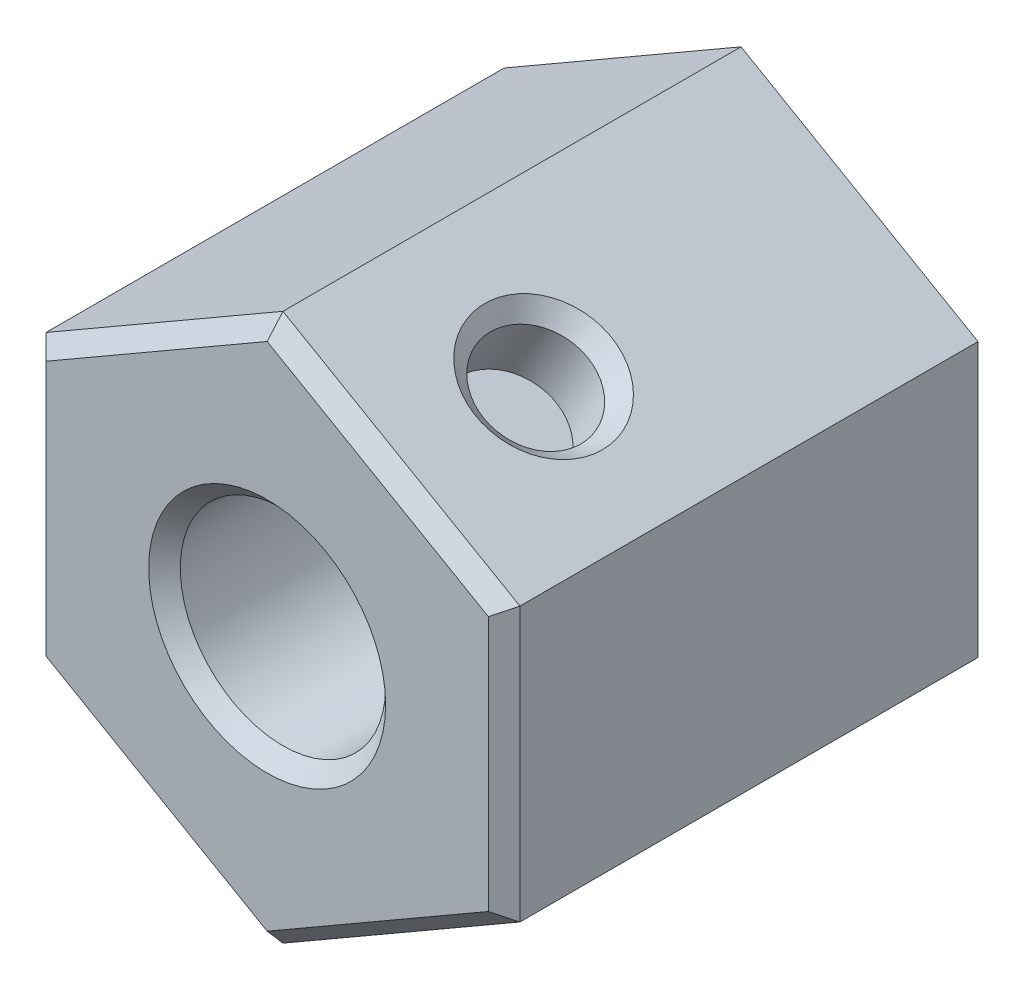
SolidWorks part; units mm, degrees
ref_plane "Front" through (0, 0, 0) normal (0, 0, 1) x (1, 0, 0)
ref_plane "Top" through (0, 0, 0) normal (0, 1, 0) x (1, 0, 0)
ref_plane "Right" through (0, 0, 0) normal (1, 0, 0) x (0, 0, -1)
sketch "Sketch1" plane through (0, 0, 0) normal (0, 0, 1) x (1, 0, 0)
  line L1 (0, 8.6603) -> (-7.5, 4.3301)
  line L2 (-7.5, 4.3301) -> (-7.5, -4.3301)
  line L3 (-7.5, -4.3301) -> (0, -8.6603)
  line L4 (0, -8.6603) -> (7.5, -4.3301)
  line L5 (7.5, -4.3301) -> (7.5, 4.3301)
  line L6 (7.5, 4.3301) -> (0, 8.6603)
  circle A0 centre (0, 0) radius 7.5 construction
  dimension "D1" = 15
extrude "Boss-Extrude1" add sketch "Sketch1" along normal blind 15
sketch "Sketch2" plane through (0, 0, 15) normal (0, 0, 1) x (1, 0, 0)
  circle A0 centre (0, 0) radius 3.25
  dimension "D1" = 6.5
extrude "Cut-Extrude1" cut sketch "Sketch2" against normal blind 15
sketch "Sketch3" plane through (0, 0, 0) normal (0, 0, -1) x (-1, 0, 0)
  line L0 (-7.5, 4.3301) -> (0, 8.6603) construction
  line L1 (0, 5.889) -> (-5.1, 2.9445)
  line L2 (-5.1, 2.9445) -> (-5.1, -2.9445)
  line L3 (-5.1, -2.9445) -> (0, -5.889)
  line L4 (0, -5.889) -> (5.1, -2.9445)
  line L5 (5.1, -2.9445) -> (5.1, 2.9445)
  line L6 (5.1, 2.9445) -> (0, 5.889)
  circle A0 centre (0, 0) radius 5.1 construction
  dimension "D1" = 10.2
extrude "Cut-Extrude2" cut sketch "Sketch3" against normal blind 2.5
sketch "Sketch4" plane through (3.75, 6.4952, 0) normal (0.5, 0.866, 0) x (0.866, -0.5, 0)
  line L0 (4.3301, 0) -> (-4.3301, 0) construction
  circle A0 centre (0, -10) radius 1.65
  point P5 (0, 0)
  dimension "D1" = 3.3
  dimension "D2" = 10
extrude "Cut-Extrude3" cut sketch "Sketch4" against normal blind 2.5
ref_axis "Axis1" through (0, 0, 2.5) along (0, 0, 1)
pattern_circular "CirPattern1" count 3 over 360 about axis through (0, 0, 15) along (0, 0, 1) of "Cut-Extrude3"
chamfer "Chamfer1" distance 0.5 angle 45 7 edges at (7.5, 0, 15) (3.75, -6.4952, 15) (-3.75, -6.4952, 15) (-7.5, 0, 15) (-3.75, 6.4952, 15) (3.75, 6.4952, 15) (3.25, 0, 15)
chamfer "Chamfer2" distance 0.5 angle 45 3 edges at (-7.5, -1.65, 10) (5.1789, -5.6702, 10) (2.3211, 7.3202, 10)
chamfer "Chamfer3" distance 0.5 angle 45 1 edges at (-3.25, 0, 2.5)
